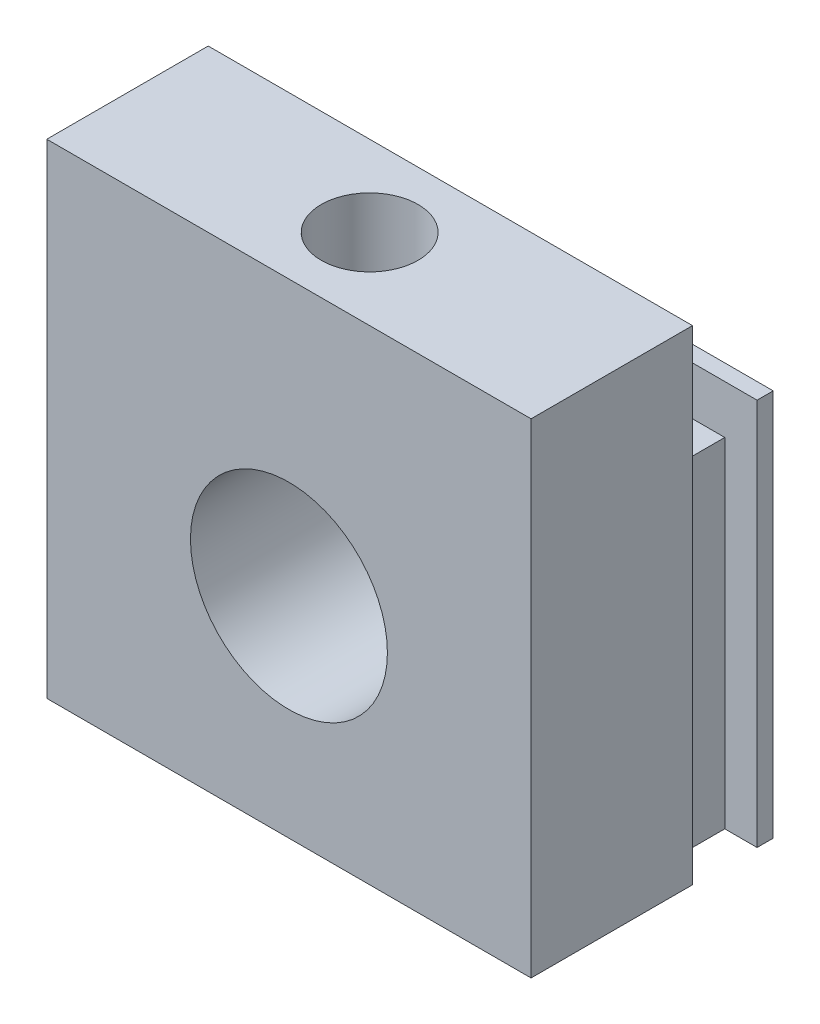
SolidWorks part; units mm, degrees
ref_plane "Plan de face" through (0, 0, 0) normal (0, 0, 1) x (1, 0, 0)
ref_plane "Plan de dessus" through (0, 0, 0) normal (0, 1, 0) x (1, 0, 0)
ref_plane "Plan de droite" through (0, 0, 0) normal (1, 0, 0) x (0, 0, -1)
sketch "Esquisse1" plane through (0, 0, 0) normal (0, 0, 1) x (1, 0, 0)
  line L1 (-7.5, 7.5) -> (7.5, 7.5)
  line L2 (-7.5, 7.5) -> (-7.5, -7.5)
  line L3 (-7.5, -7.5) -> (7.5, -7.5)
  line L4 (7.5, 7.5) -> (7.5, -7.5)
  dimension "D1" = 15
  dimension "D2" = 15
  dimension "D3" = 7.5
  dimension "D4" = 7.5
extrude "Boss.-Extru.1" add sketch "Esquisse1" along normal blind 5
sketch "Esquisse2" plane through (0, 7.5, 0) normal (0, 1, 0) x (1, 0, 0)
  line L0 (7.5, 0) -> (-7.5, 0) construction
  line L1 (7.5, -5) -> (7.5, 0) construction
  circle A0 centre (0, -2.5) radius 1.5
  point P0 (0, -2.5)
  dimension "D3" = 3
  dimension "D1" = 2.5
  dimension "D2" = 7.5
extrude "Enlèv. mat.-Extru.1" cut sketch "Esquisse2" against normal blind 3
sketch "Esquisse3" plane through (0, 0, 0) normal (0, 0, -1) x (-1, 0, 0)
  line L0 (7.5, -7.5) -> (-7.5, -7.5) construction
  line L1 (-6.5, -7.5) -> (6.5, -7.5)
  line L2 (-6.5, -7.5) -> (-6.5, 3)
  line L3 (-6.5, 3) -> (6.5, 3)
  line L4 (6.5, -7.5) -> (6.5, 3)
  dimension "D1" = 10.5
  dimension "D2" = 1
  dimension "D3" = 1
extrude "Boss.-Extru.2" add sketch "Esquisse3" along normal blind 2 contours L2 L1 L4 L3
sketch "Esquisse4" plane through (0, 0, -2) normal (0, 0, -1) x (-1, 0, 0)
  line L0 (-6.5, -7.5) -> (6.5, -7.5) construction
  line L1 (-7.5, -7.5) -> (7.5, -7.5)
  line L2 (-7.5, -7.5) -> (-7.5, 4.5)
  line L3 (-7.5, 4.5) -> (7.5, 4.5)
  line L4 (7.5, -7.5) -> (7.5, 4.5)
  dimension "D1" = 0
  dimension "D2" = 0
  dimension "D3" = 12
extrude "Boss.-Extru.3" add sketch "Esquisse4" along normal blind 0.5 contours L2 L1 L4 L3
sketch "Esquisse5" plane through (0, 0, -2.5) normal (0, 0, -1) x (-1, 0, 0)
  line L0 (-7.5, 4.5) -> (7.5, 4.5) construction
  line L1 (7.5, -7.5) -> (7.5, 4.5) construction
  circle A0 centre (0, -1) radius 3.05
  dimension "D3" = 6.1
  dimension "D1" = 5.5
  dimension "D2" = 7.5
extrude "Enlèv. mat.-Extru.2" cut sketch "Esquisse5" against normal blind 1 contours A0
extrude "Enlèv. mat.-Extru.3" cut sketch "Esquisse5<3>" against normal blind 15
sketch "Esquisse5<3>" plane through (0, 0, -2.5) normal (0, 0, -1) x (-1, 0, 0) same geometry as "Esquisse5"
